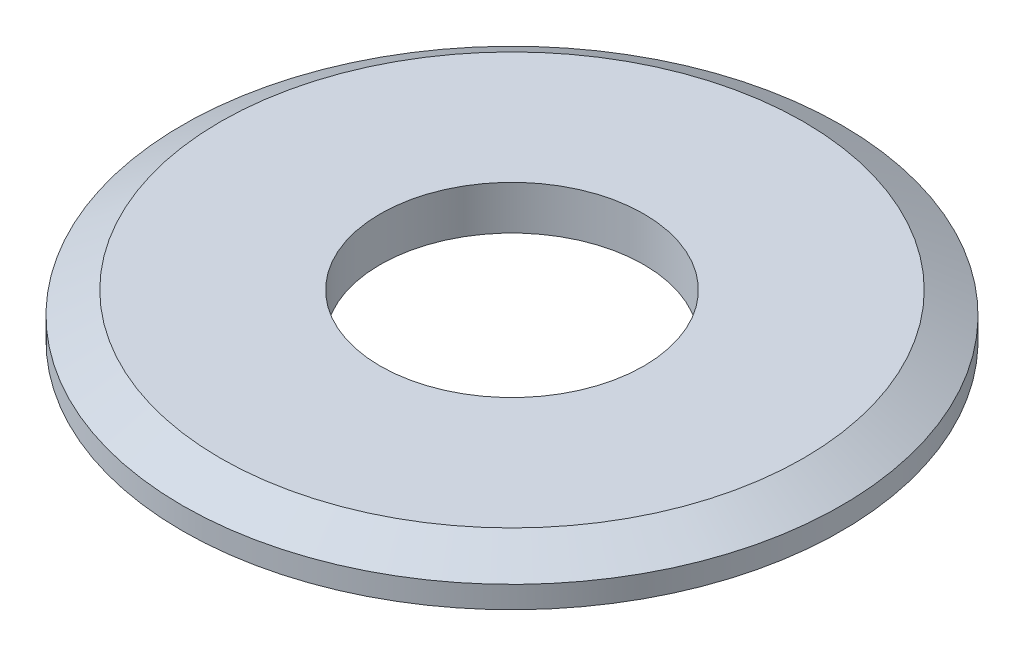
SolidWorks part; units mm, degrees
ref_plane "Front Plane" through (0, 0, 0) normal (0, 0, 1) x (1, 0, 0)
ref_plane "Top Plane" through (0, 0, 0) normal (0, 1, 0) x (1, 0, 0)
ref_plane "Right Plane" through (0, 0, 0) normal (1, 0, 0) x (0, 0, -1)
sketch "Sketch1" plane through (0, 0, 0) normal (0, 1, 0) x (1, 0, 0)
  circle A0 centre (0, 0) radius 7.5
  dimension "D1" = 15
extrude "Boss-Extrude1" add sketch "Sketch1" along normal blind 1 contours A0
chamfer "Chamfer1" distance 0.5 angle 60 1 edges at (0, 1, 7.5) first distance on face at (0, 1, 7.5)
sketch "Sketch2" plane through (0, 1, 0) normal (0, 1, 0) x (1, 0, 0)
  circle A0 centre (0, 0) radius 3
  dimension "D1" = 6
extrude "Cut-Extrude1" cut sketch "Sketch2" against normal blind 1
